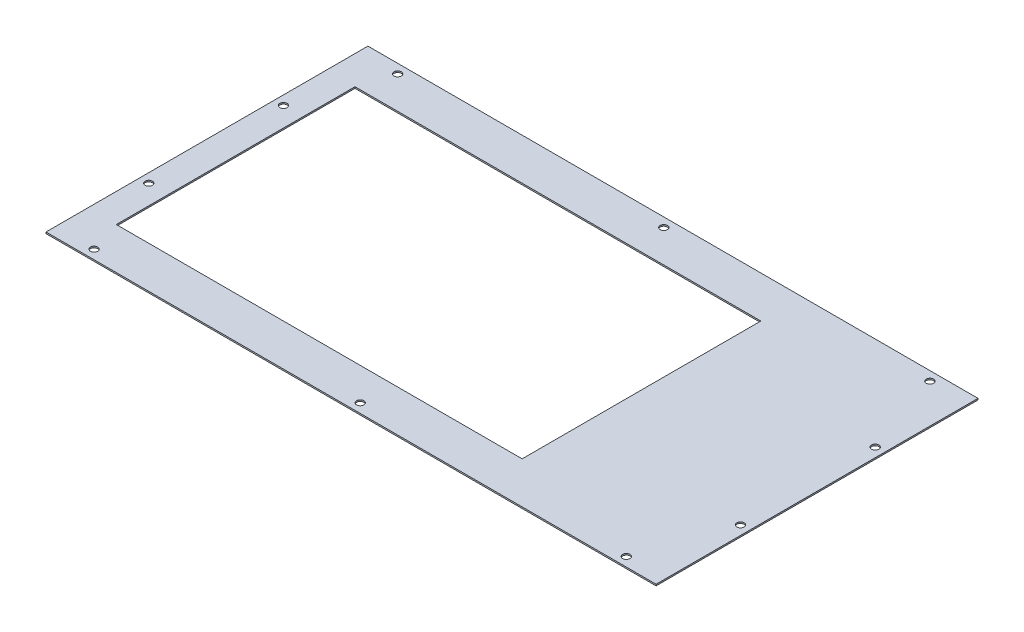
SolidWorks part; units mm, degrees
ref_plane "Front Plane" through (0, 0, 0) normal (0, 0, 1) x (1, 0, 0)
ref_plane "Top Plane" through (0, 0, 0) normal (0, 1, 0) x (1, 0, 0)
ref_plane "Right Plane" through (0, 0, 0) normal (1, 0, 0) x (0, 0, -1)
sketch "Sketch1" plane through (0, 0, 0) normal (0, 1, 0) x (1, 0, 0)
  line L0 (0, 87.7) -> (0, -87.7) construction
  line L1 (-166.2, -87.7) -> (166.2, -87.7)
  line L2 (-166.2, -87.7) -> (-166.2, 87.7)
  line L3 (-166.2, 87.7) -> (166.2, 87.7)
  line L4 (166.2, -87.7) -> (166.2, 87.7)
  line L5 (-166.2, -87.7) -> (166.2, 87.7) construction
  line L6 (-166.2, 87.7) -> (166.2, -87.7) construction
  line L7 (-166.2, 0) -> (166.2, 0) construction
  circle A0 centre (0, 82.7) radius 2
  circle A1 centre (145, 82.7) radius 2
  circle A2 centre (-145, 82.7) radius 2
  circle A3 centre (-161.2, 36.7) radius 2
  circle A4 centre (161.2, 36.7) radius 2
  circle A5 centre (161.2, -36.7) radius 2
  circle A6 centre (145, -82.7) radius 2
  circle A7 centre (0, -82.7) radius 2
  circle A8 centre (-145, -82.7) radius 2
  circle A9 centre (-161.2, -36.7) radius 2
  point P0 (0, 0)
  dimension "D3" = 5
  dimension "D4" = 145
  dimension "D7" = 5
  dimension "D1" = 332.4
  dimension "D2" = 175.4
  dimension "D5" = 145
  dimension "D6" = 21.2
  dimension "D8" = 51
sheet metal parameters "Sheet-Metal1" thickness 0.8 parameters "D1"=0.8
base flange "Base-Flange1" sketch "Sketch1" thickness 0.8 reverse thickness direction no parameters "D1"=0.8
sketch "Sketch2" plane through (0, 0, 0) normal (0, 1, 0) x (1, 0, 0)
  line L1 (-150.56, 65.035) -> (70.56, 65.035)
  line L2 (-150.56, 65.035) -> (-150.56, -65.035)
  line L3 (-150.56, -65.035) -> (70.56, -65.035)
  line L4 (70.56, 65.035) -> (70.56, -65.035)
  line L5 (-150.56, 65.035) -> (70.56, -65.035) construction
  line L6 (-150.56, -65.035) -> (70.56, 65.035) construction
  point P0 (-40, 0)
  dimension "D1" = 40
  dimension "D2" = 130.07
  dimension "D3" = 221.12
  dimension "D4" = 256.539
extrude "Cut-Extrude1" cut sketch "Sketch2" against normal blind 10 normal cut yes
flat pattern "Flat-Pattern1" [suppressed]
sketch "Bend-Lines1" plane through (0, 0, 0) normal (0, 1, 0) x (-1, 0, 0)
